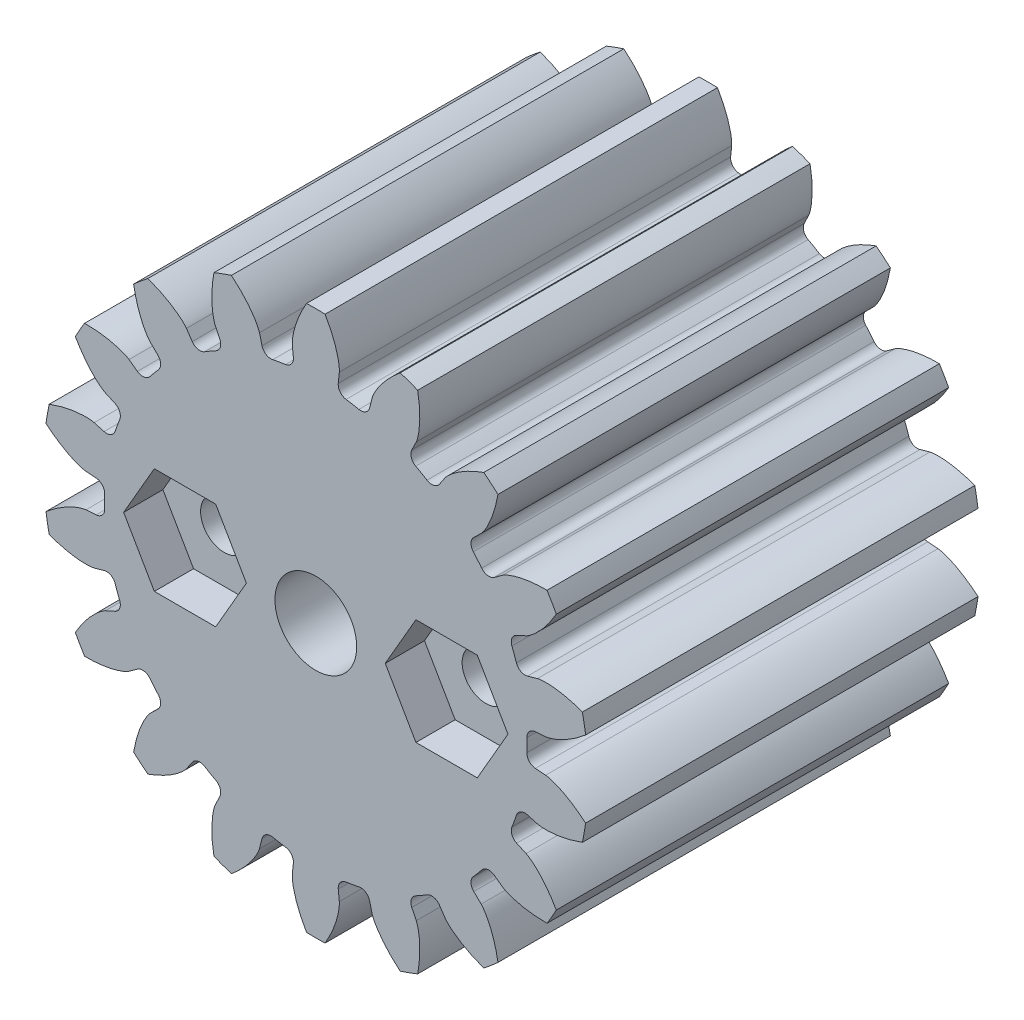
SolidWorks part; units mm, degrees
ref_plane "Front Plane" through (0, 0, 0) normal (0, 0, 1) x (1, 0, 0)
ref_plane "Top Plane" through (0, 0, 0) normal (0, 1, 0) x (1, 0, 0)
ref_plane "Right Plane" through (0, 0, 0) normal (1, 0, 0) x (0, 0, -1)
sketch "Sketch1" plane through (0, 0, 0) normal (0, 0, 1) x (1, 0, 0)
  line L0 (0, 0) -> (0, 9.525) construction
  line L1 (-3.0613, 10.6392) -> (3.0613, 8.4108) construction
  circle A0 centre (0, 0) radius 8.2021 construction
  circle A1 centre (0, 0) radius 10.5833 construction
  circle A2 centre (0, 0) radius 9.525 construction
  circle A3 centre (0, 0) radius 8.9506 construction
  circle A4 centre (0, 0) radius 2.3813 construction
  circle A5 centre (0, 0) radius 6.858 construction
  point P8 (304.8, 0)
  point P13 (228.6, 0)
  dimension "OD | Outside Diameter" = 21.1667
  dimension "Root Diameter" = 16.4042
  dimension "Gear Pitch Diameter" = 19.05
  dimension "Base Diameter" = 17.9011
  dimension "For Shaft Diameter" = 4.7625
  dimension "Hub Diameter" = 13.716
  dimension "Pressure Angle" = 20
  dimension "Number of Teeth" = 457.2
  dimension "Gear Pitch | Diametral Pitch" = 609.6
sketch "Sketch2" plane through (0, 0, 0) normal (1, 0, 0) x (0, 0, -1)
  line L0 (-6.35, 0) -> (6.35, 0) construction
  line L1 (-6.35, 10.5833) -> (6.35, 10.5833) construction
  point P2 (0, 10.5833)
  point P4 (0, 0)
  point P6 (0, 10.5833)
  dimension "Overall Width" = 12.7
  dimension "Hub Width" = 6.35
  dimension "Face Width" = 6.35
sketch "Sketch3" plane through (0, 0, 0) normal (0, 0, 1) x (1, 0, 0)
  circle A0 centre (0, 0) radius 10.5833
  circle A1 centre (0, 0) radius 10.5833 construction
extrude "Boss-Extrude1" add sketch "Sketch3" against normal blind 15.24
sketch "Sketch4" plane through (0, 0, 0) normal (0, 0, 1) x (1, 0, 0)
  line L0 (0, 0) -> (8.1806, 0.593) construction
  line L2 (0, 0) -> (8.1806, -0.593) construction
  line L4 (8.1806, 0.593) -> (8.9271, 0.6471)
  line L5 (8.9271, -0.6471) -> (8.1806, -0.593)
  arc A0 (8.1806, 0.593) -> (8.1806, -0.593) centre (0, 0) cw
  arc A3 (10.4791, 1.4815) -> (10.4791, -1.4815) centre (0, 0) cw
  circle A4 centre (0, 0) radius 10.5833 construction
  spline S0 degree 4 poles (8.9271, 0.6471) (8.9298, 0.6473) (8.9371, 0.6481) (8.951, 0.6499) (8.9735, 0.6535) (9.0022, 0.659) (9.039, 0.6671) (9.0823, 0.6779) (9.1296, 0.6912) (9.1807, 0.7071) (9.2315, 0.7243) (9.2819, 0.7426) (9.3319, 0.762) (9.3922, 0.7867) (9.464, 0.8182) (9.5473, 0.8575) (9.6409, 0.905) (9.7354, 0.9567) (9.8276, 1.0102) (9.9198, 1.0673) (10.0083, 1.1246) (10.0992, 1.1871) (10.1825, 1.2464) (10.2747, 1.3161) (10.3487, 1.3734) (10.4449, 1.4524) (10.5013, 1.5001) (10.5668, 1.5571) (10.5956, 1.5831) (10.6134, 1.599) knots 0 0 0 0 0 0.005377 0.015084 0.028532 0.04661 0.064855 0.092111 0.119476 0.146842 0.174209 0.201575 0.228941 0.256307 0.307035 0.361767 0.4165 0.471232 0.525964 0.580697 0.635429 0.690161 0.744894 0.799626 0.854358 0.909091 0.954545 1 1 1 1 1 construction
  spline S1 degree 4 poles (8.9271, 0.6471) (8.9298, 0.6473) (8.9371, 0.6481) (8.951, 0.6499) (8.9735, 0.6535) (9.0022, 0.659) (9.039, 0.6671) (9.0823, 0.6779) (9.1296, 0.6912) (9.1807, 0.7071) (9.2315, 0.7243) (9.2819, 0.7426) (9.3319, 0.762) (9.3922, 0.7867) (9.464, 0.8182) (9.5473, 0.8575) (9.6409, 0.905) (9.7354, 0.9567) (9.8276, 1.0102) (9.9198, 1.0673) (10.0083, 1.1246) (10.0992, 1.1871) (10.1825, 1.2464) (10.2747, 1.3161) (10.3487, 1.3734) (10.424, 1.4353) (10.4605, 1.4658) (10.4791, 1.4815) knots 0 0 0 0 0 0.005377 0.015084 0.028532 0.04661 0.064855 0.092111 0.119476 0.146842 0.174209 0.201575 0.228941 0.256307 0.307035 0.361767 0.4165 0.471232 0.525964 0.580697 0.635429 0.690161 0.744894 0.799626 0.854358 0.909091 0.909091 0.909091 0.909091 0.909091
  spline S2 degree 4 poles (8.9271, -0.6471) (8.9298, -0.6473) (8.9371, -0.6481) (8.951, -0.6499) (8.9735, -0.6535) (9.0022, -0.659) (9.039, -0.6671) (9.0823, -0.6779) (9.1296, -0.6912) (9.1807, -0.7071) (9.2315, -0.7243) (9.2819, -0.7426) (9.3319, -0.762) (9.3922, -0.7867) (9.464, -0.8182) (9.5473, -0.8575) (9.6409, -0.905) (9.7354, -0.9567) (9.8276, -1.0102) (9.9198, -1.0673) (10.0083, -1.1246) (10.0992, -1.1871) (10.1825, -1.2464) (10.2747, -1.3161) (10.3487, -1.3734) (10.4449, -1.4524) (10.5013, -1.5001) (10.5668, -1.5571) (10.5956, -1.5831) (10.6134, -1.599) knots 0 0 0 0 0 0.005377 0.015084 0.028532 0.04661 0.064855 0.092111 0.119476 0.146842 0.174209 0.201575 0.228941 0.256307 0.307035 0.361767 0.4165 0.471232 0.525964 0.580697 0.635429 0.690161 0.744894 0.799626 0.854358 0.909091 0.954545 1 1 1 1 1 construction
  spline S3 degree 4 poles (8.9271, -0.6471) (8.9298, -0.6473) (8.9371, -0.6481) (8.951, -0.6499) (8.9735, -0.6535) (9.0022, -0.659) (9.039, -0.6671) (9.0823, -0.6779) (9.1296, -0.6912) (9.1807, -0.7071) (9.2315, -0.7243) (9.2819, -0.7426) (9.3319, -0.762) (9.3922, -0.7867) (9.464, -0.8182) (9.5473, -0.8575) (9.6409, -0.905) (9.7354, -0.9567) (9.8276, -1.0102) (9.9198, -1.0673) (10.0083, -1.1246) (10.0992, -1.1871) (10.1825, -1.2464) (10.2747, -1.3161) (10.3487, -1.3734) (10.424, -1.4353) (10.4605, -1.4658) (10.4791, -1.4815) knots 0 0 0 0 0 0.005377 0.015084 0.028532 0.04661 0.064855 0.092111 0.119476 0.146842 0.174209 0.201575 0.228941 0.256307 0.307035 0.361767 0.4165 0.471232 0.525964 0.580697 0.635429 0.690161 0.744894 0.799626 0.854358 0.909091 0.909091 0.909091 0.909091 0.909091
  dimension "D1" = 16.4042
extrude "Cut-Extrude1" cut sketch "Sketch4" against normal through all both and the other way through all
fillet "Fillet1" radius 0.3551 2 edges at (8.1806, -0.593, -7.62) (8.1806, 0.593, -7.62)
pattern_circular "CirPattern1" count 18 over 360 about axis through (0, 0, 6.35) along (0, 0, -1) of "Cut-Extrude1", "Fillet1"
scale "Scale3" scale about origin uniform scaling yes scale factor 2
sketch "Sketch10" plane through (0, 0, 0) normal (0, 0, 1) x (1, 0, 0)
  circle A0 centre (0, 0) radius 3.175
  dimension "D1" = 6.35
extrude "Cut-Extrude4" cut sketch "Sketch10" against normal blind 7.62
sketch "Sketch11" plane through (0, 0, -30.48) normal (0, 0, -1) x (-1, 0, 0)
  circle A0 centre (0, 0) radius 3.048
  dimension "D1" = 6.096
extrude "Cut-Extrude5" cut sketch "Sketch11" against normal blind 2.54
sketch "Sketch12" plane through (0, 0, -30.48) normal (0, 0, -1) x (-1, 0, 0)
  circle A0 centre (0, 0) radius 19.05
sketch "Sketch13" plane through (0, 0, 0) normal (0, 0, 1) x (1, 0, 0)
  line L0 (0, 0) -> (-0.0634, 10.6281) construction
  line L1 (-5.394, 0) -> (-7.777, 4.1275)
  line L2 (-7.777, 4.1275) -> (-12.543, 4.1275)
  line L3 (-12.543, 4.1275) -> (-14.926, 0)
  line L4 (-14.926, 0) -> (-12.543, -4.1275)
  line L5 (-12.543, -4.1275) -> (-7.777, -4.1275)
  line L6 (-7.777, -4.1275) -> (-5.394, 0)
  line L7 (14.926, 0) -> (12.543, 4.1275)
  line L8 (12.543, 4.1275) -> (7.777, 4.1275)
  line L9 (7.777, 4.1275) -> (5.394, 0)
  line L10 (5.394, 0) -> (7.777, -4.1275)
  line L11 (7.777, -4.1275) -> (12.543, -4.1275)
  line L12 (12.543, -4.1275) -> (14.926, 0)
  circle A0 centre (-10.16, 0) radius 4.1275 construction
  circle A1 centre (10.16, 0) radius 4.1275 construction
  dimension "D1" = 8.255
  dimension "D2" = 8.255
  dimension "D3" = 10.16
  dimension "D4" = 10.16
extrude "Cut-Extrude6" cut sketch "Sketch13" against normal blind 3.048
sketch "Sketch14" plane through (0, 0, -3.048) normal (0, 0, 1) x (1, 0, 0)
  line L0 (-7.777, 4.1275) -> (-12.543, 4.1275) construction
  line L1 (12.543, 4.1275) -> (7.777, 4.1275) construction
  circle A0 centre (-10.16, 0) radius 1.8415
  circle A1 centre (10.16, 0) radius 1.8415
  point P6 (-10.16, 4.1275)
  point P9 (10.16, 4.1275)
  dimension "D1" = 3.683
  dimension "D2" = 3.683
extrude "Cut-Extrude7" cut sketch "Sketch14" against normal blind 12.7
equation "\"Root Diameter@Sketch1\"=\"Root Diameter\""
equation "\"OD | Outside Diameter@Sketch1\"=\"Outside Diameter\""
equation "\"D1@CirPattern1\"=\"Number of Teeth\""
equation "\"Diametral Pitch\"= 24"
equation "\"Number of Teeth\"= 18"
equation "\"Pressure Angle\"=20"
equation "\"Pitch Diameter\"= \"Number of Teeth\" / \"Diametral Pitch\""
equation "\"Base Diameter\"= \"Pitch Diameter\" * cos ( \"Pressure Angle\" )"
equation "\"Outside Diameter\"= ( \"Number of Teeth\" + 2 ) / \"Diametral Pitch\""
equation "\"Dedendum\"= 1.25 / \"Diametral Pitch\""
equation "\"Root Diameter\"= \"Pitch Diameter\" - ( 2 * \"Dedendum\" )"
equation "\"Pitch Angle\"= 360deg / \"Number of Teeth\""
equation "\"Alpha\"= sqr ( \"Pitch Diameter\" ^ 2 - \"Base Diameter\" ^ 2 ) / \"Base Diameter\" * 180 / PI - \"Pressure Angle\""
equation "\"Beta\"= ( \"Pitch Angle\" / 4 - \"Alpha\" )"
equation "\"Phi\"= sqr ( ( \"Outside Diameter\" / 2 ) ^ 2 - ( \"Base Diameter\" / 2 ) ^ 2 ) / ( \"Base Diameter\" / 2 )"
equation "\"Addendum\"= 1 / \"Diametral Pitch\""
equation "\"WorkingDepth\"= 2 / \"Diametral Pitch\""
equation "\"WholeDepth\"= 2.25 / \"Diametral Pitch\""
equation "\"Clearance\"= 0.25 / \"Diametral Pitch\""
equation "\"ToothThickness\"= ( pi * 2 ) / \"Diametral Pitch\""
equation "\"CircularPitch\"= pi / \"Diametral Pitch\""
equation "\"Number of Teeth@Sketch1\"=\"Number of Teeth\""
equation "\"Gear Pitch | Diametral Pitch@Sketch1\"=\"Diametral Pitch\""
equation "\"Pressure Angle@Sketch1\"=\"Pressure Angle\""
equation "\"Gear Pitch Diameter@Sketch1\"=\"Pitch Diameter\""
equation "\"Base Diameter@Sketch1\"=\"Base Diameter\""
equation "\"Fillet\"= \"Clearance\" * cos ( \"Pressure Angle\" ) * tan ( ( 90 + \"Pressure Angle\" ) / 2 )"
equation "\"D1@Fillet1\"=\"Fillet\""
equation "\"D1@Sketch4\"=if( \"Base Diameter\">\"Root Diameter\",\"Root Diameter\",\"Base Diameter\"-.00001)"
equation "\"D1@Fillet2\"=\"Fillet\""
